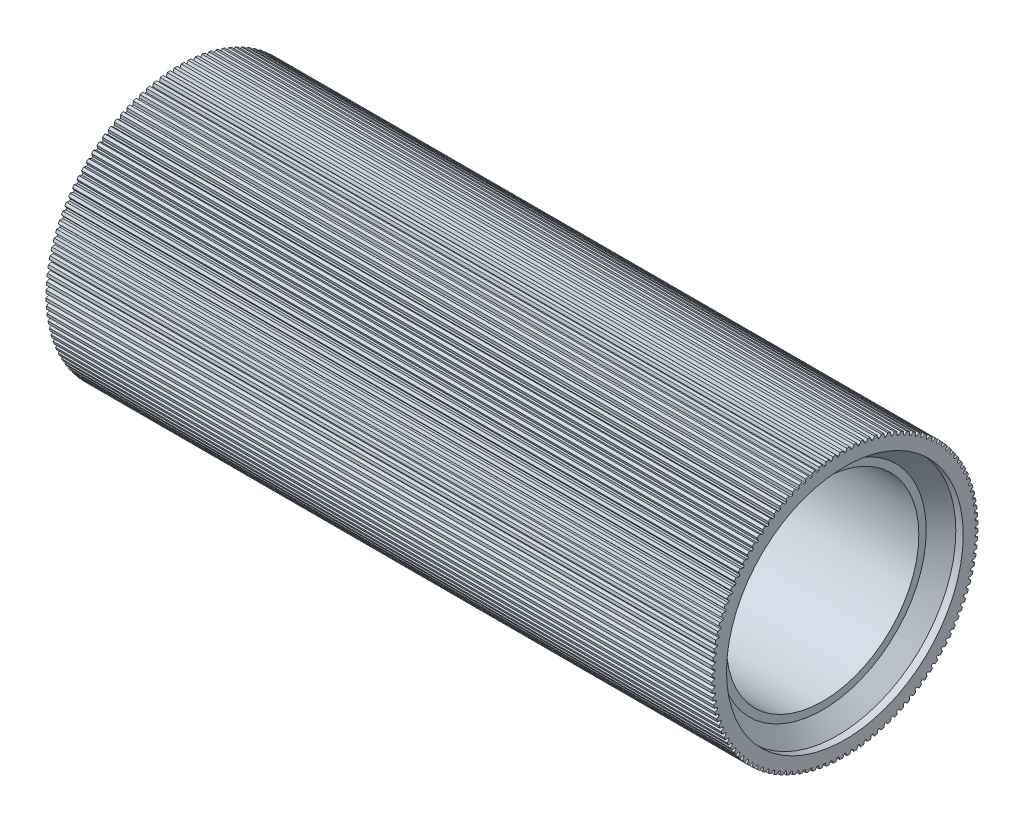
SolidWorks part; units mm, degrees
ref_plane "Front Plane" through (0, 0, 0) normal (0, 0, 1) x (1, 0, 0)
ref_plane "Top Plane" through (0, 0, 0) normal (0, 1, 0) x (1, 0, 0)
ref_plane "Right Plane" through (0, 0, 0) normal (1, 0, 0) x (0, 0, -1)
sketch "Sketch1" plane through (0, 0, 0) normal (0, 0, 1) x (1, 0, 0)
  line L0 (0, 0) -> (450, 0) construction
  line L1 (0, 0) -> (0, 90)
  line L2 (0, 90) -> (450, 90)
  line L3 (450, 90) -> (450, 80)
  line L4 (450, 80) -> (435, 80)
  line L5 (435, 80) -> (435, 65)
  line L6 (435, 65) -> (15, 65)
  line L7 (15, 65) -> (15, 80)
  line L8 (15, 80) -> (0, 80)
  line L9 (450, 90) -> (450, 0)
  dimension "D1" = 450
  dimension "D2" = 90
  dimension "D3" = 10
  dimension "D4" = 10
  dimension "D5" = 15
  dimension "D6" = 420
  dimension "D7" = 15
  dimension "D8" = 15
revolve "Revolve1" add sketch "Sketch1" angle 360 about L0 region at (225, 77.7083, 0)
chamfer "Chamfer2" distance 10 angle 45 1 edges at (435, 0, 80)
sketch "Sketch4" plane through (0, 0, 0) normal (1, 0, 0) x (0, 0, -1)
  line L0 (0, 0) -> (0, 90) construction
  line L1 (-0.5, 88) -> (0.5, 88)
  line L2 (-0.5, 88) -> (-1.5, 90.2913)
  line L3 (-1.5, 90.2913) -> (1.5, 90.2913)
  line L4 (0.5, 88) -> (1.5, 90.2913)
  circle A0 centre (0, 0) radius 90 construction
  point P9 (0, 88)
  point P11 (0, 90.2913)
  dimension "D1" = 88
  dimension "D2" = 1
  dimension "D3" = 3
  dimension "D4" = 2.5
extrude "Cut-Extrude2" cut sketch "Sketch4" along normal through all contours L4 L3 L2 L1
pattern_circular "CirPattern3" count 120 over 360 about axis through (450, 0, 0) along (-1, 0, 0) of "Cut-Extrude2"
